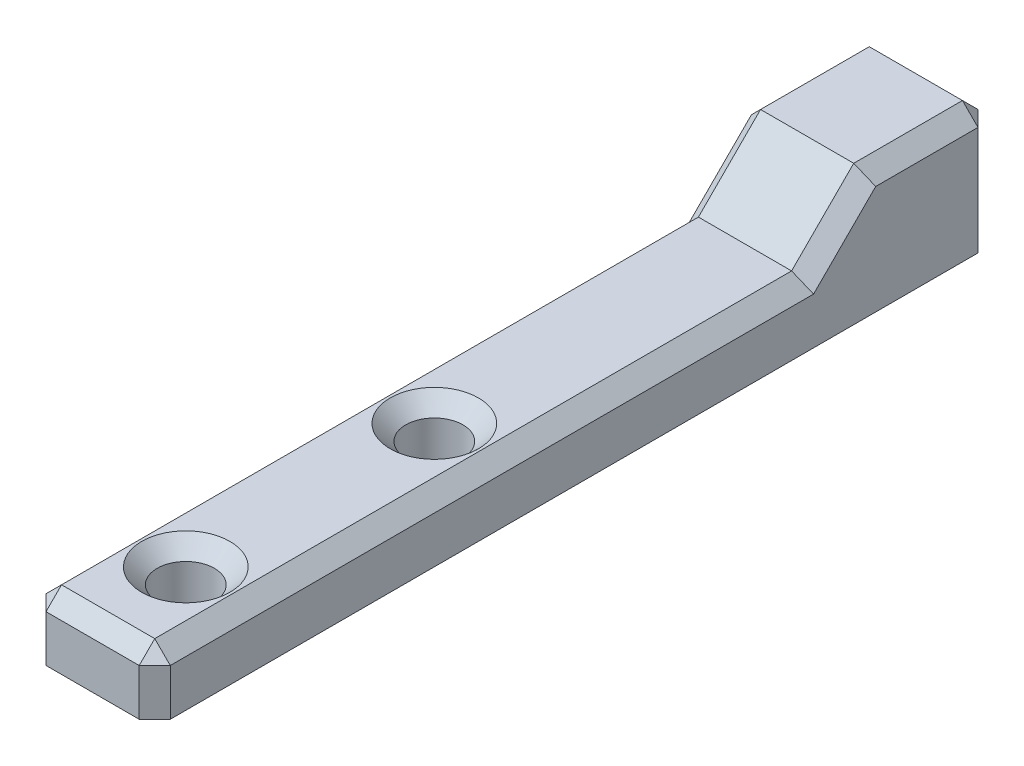
SolidWorks part; units mm, degrees
ref_plane "Front Plane" through (0, 0, 0) normal (0, 0, 1) x (1, 0, 0)
ref_plane "Top Plane" through (0, 0, 0) normal (0, 1, 0) x (1, 0, 0)
ref_plane "Right Plane" through (0, 0, 0) normal (1, 0, 0) x (0, 0, -1)
sketch "Sketch1" plane through (0, 0, 0) normal (0, 1, 0) x (1, 0, 0)
  line L1 (0, 0) -> (12.7, 0)
  line L2 (0, 0) -> (0, 85.725)
  line L3 (0, 85.725) -> (12.7, 85.725)
  line L4 (12.7, 0) -> (12.7, 85.725)
  circle A0 centre (6.35, 9.525) radius 2.921
  circle A1 centre (6.35, 34.925) radius 2.921
  dimension "D3" = 5.842
  dimension "D1" = 12.7
  dimension "0.375" = 9.525
  dimension "D4" = 25.4
  dimension "D5" = 50.8
extrude "Boss-Extrude1" add sketch "Sketch1" along normal blind 12.7
sketch "Sketch2" plane through (12.7, 0, 0) normal (1, 0, 0) x (0, 0, -1)
  line L0 (85.725, 12.7) -> (85.725, 0) construction
  line L1 (0, 12.7) -> (73.025, 12.7)
  line L2 (0, 12.7) -> (0, 6.35)
  line L3 (0, 6.35) -> (73.025, 6.35)
  line L4 (73.025, 12.7) -> (73.025, 6.35)
  dimension "D1" = 12.7
  dimension "D2" = 6.35
extrude "Cut-Extrude1" cut sketch "Sketch2" against normal through all
chamfer "Chamfer1" distance 6.35 angle 45 1 edges at (6.35, 6.35, -73.025)
chamfer "Chamfer2" distance 1.5875 angle 45 14 edges at (0, 3.175, 0) (12.7, 3.175, 0) (0, 6.35, -85.725) (12.7, 6.35, -85.725) (0, 9.525, -69.85) (0, 12.7, -79.375) (6.35, 12.7, -85.725) (12.7, 12.7, -79.375) (12.7, 9.525, -69.85) (0, 6.35, -33.3375) (6.35, 6.35, 0) (12.7, 6.35, -33.3375) (6.35, 6.35, -12.446) (6.35, 6.35, -37.846)
